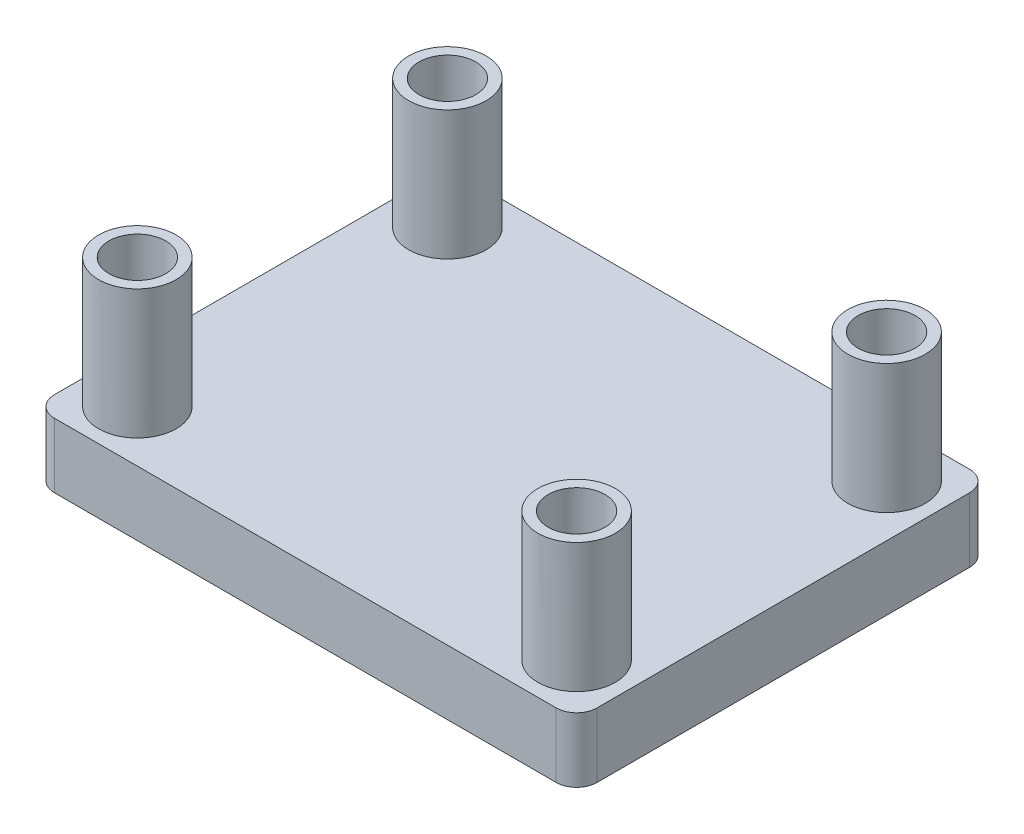
SolidWorks part; units mm, degrees
ref_plane "Front" through (0, 0, 0) normal (0, 0, 1) x (1, 0, 0)
ref_plane "Top" through (0, 0, 0) normal (0, 1, 0) x (1, 0, 0)
ref_plane "Right" through (0, 0, 0) normal (1, 0, 0) x (0, 0, -1)
sketch "Sketch1" plane through (0, 0, 0) normal (0, 1, 0) x (1, 0, 0)
  line L1 (-23.7864, 11.5944) -> (2.8836, 11.5944)
  line L2 (-23.7864, 11.5944) -> (-23.7864, -8.7256)
  line L3 (-23.7864, -8.7256) -> (2.8836, -8.7256)
  line L4 (2.8836, 11.5944) -> (2.8836, -8.7256)
  dimension "D1" = 20.32
  dimension "D2" = 26.67
extrude "Boss-Extrude1" add sketch "Sketch1" along normal blind 3.175
sketch "Sketch2" plane through (0, 3.175, 0) normal (0, 1, 0) x (1, 0, 0)
  line L0 (-23.7864, 11.5944) -> (-23.7864, -8.7256) construction
  line L2 (2.8836, 11.5944) -> (-23.7864, 11.5944) construction
  line L3 (2.8836, -8.7256) -> (2.8836, 11.5944) construction
  line L4 (-23.7864, 1.4344) -> (2.8836, 1.4344) construction
  circle A0 centre (-21.2464, 9.0544) radius 1.905
  circle A1 centre (-21.2464, 9.0544) radius 1.397
  circle A2 centre (0.3436, 9.0544) radius 1.905
  circle A3 centre (0.3436, 9.0544) radius 1.905
  circle A4 centre (0.3436, 9.0544) radius 1.397
  circle A5 centre (0.3436, -6.1856) radius 1.397
  circle A6 centre (0.3436, -6.1856) radius 1.905
  circle A7 centre (0.3436, -6.1856) radius 1.905
  circle A8 centre (-21.2464, -6.1856) radius 1.397
  circle A9 centre (-21.2464, -6.1856) radius 1.905
  dimension "D3" = 3.81
  dimension "D4" = 2.794
  dimension "D5" = 3.81
  dimension "D6" = 2.794
  dimension "D1" = 2.54
  dimension "D2" = 2.54
  dimension "D7" = 2.54
  dimension "D8" = 2.54
extrude "Boss-Extrude2" add sketch "Sketch2" along normal blind 6.35 contours A0 A1 | A2 A4 | A5 | A8 | A9 | A6 region at (-23.0975, 3.175, -9.0544) region at (-1.5075, 3.175, -9.0544) region at (0.3436, 3.175, 6.1856) region at (-21.2464, 3.175, 6.1856)
fillet "Fillet1" radius 1 4 edges at (-23.7864, 1.5875, -11.5944) (-23.7864, 1.5875, 8.7256) (2.8836, 1.5875, -11.5944) (2.8836, 1.5875, 8.7256)
